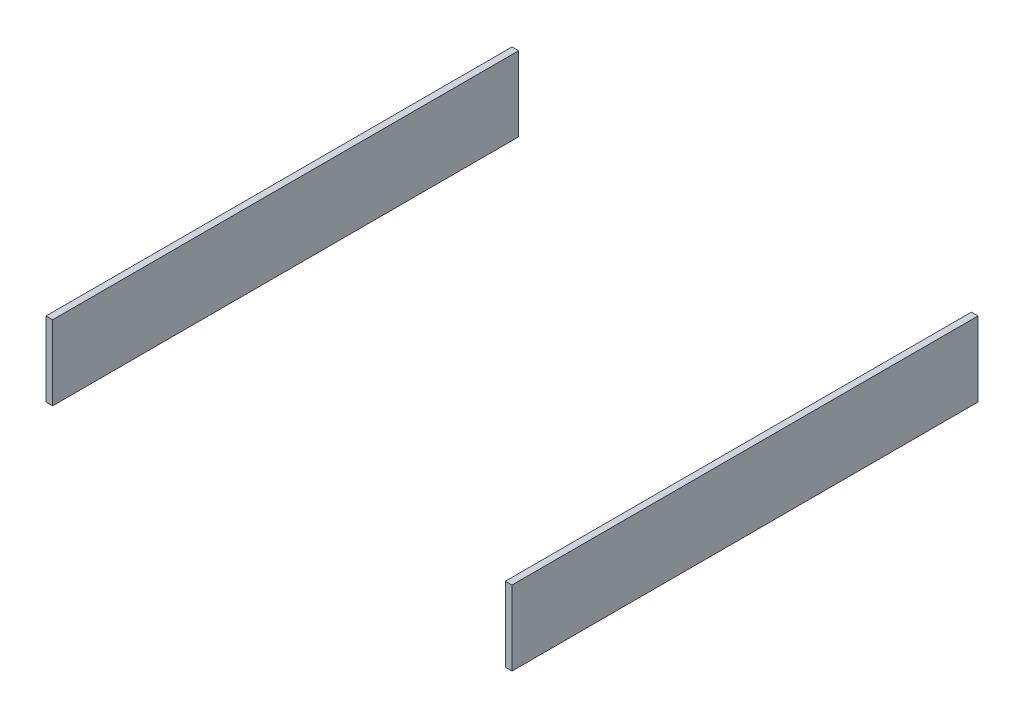
SolidWorks part; units mm, degrees
ref_plane "Front Plane" through (0, 0, 0) normal (0, 0, 1) x (1, 0, 0)
ref_plane "Top Plane" through (0, 0, 0) normal (0, 1, 0) x (1, 0, 0)
ref_plane "Right Plane" through (0, 0, 0) normal (1, 0, 0) x (0, 0, -1)
sketch "Sketch1" plane through (0, 0, 0) normal (0, 1, 0) x (1, 0, 0)
  line L1 (125, -125) -> (-125, -125)
  line L2 (125, -125) -> (125, 125)
  line L3 (125, 125) -> (-125, 125)
  line L4 (-125, -125) -> (-125, 125)
  line L5 (125, -125) -> (-125, 125) construction
  line L6 (125, 125) -> (-125, -125) construction
  arc A0 (125, -125) -> (-125, -125) centre (0, -60.5635) cw
  point P0 (0, 0)
  dimension "D3" = 64.4365
  dimension "D1" = 250
  dimension "D2" = 250
extrude "Boss-Extrude1" add sketch "Sketch1" along normal blind 1 rebuild error yes
sketch "Sketch2" plane through (0, 1, 0) normal (0, 1, 0) x (1, 0, 0)
  line L0 (-125, -125) -> (125, -125) construction
  line L1 (-125, 125) -> (-121.443, 125)
  line L2 (-125, 125) -> (-125, -125)
  line L3 (-125, -125) -> (-121.443, -125)
  line L4 (-121.443, 125) -> (-121.443, -125)
  line L5 (0, 0) -> (0, 46.0469) construction
  line L6 (121.443, 125) -> (121.443, -125)
  line L7 (125, -125) -> (121.443, -125)
  line L8 (125, 125) -> (125, -125)
  line L9 (125, 125) -> (121.443, 125)
extrude "Boss-Extrude2" add sketch "Sketch2" along normal blind 40
